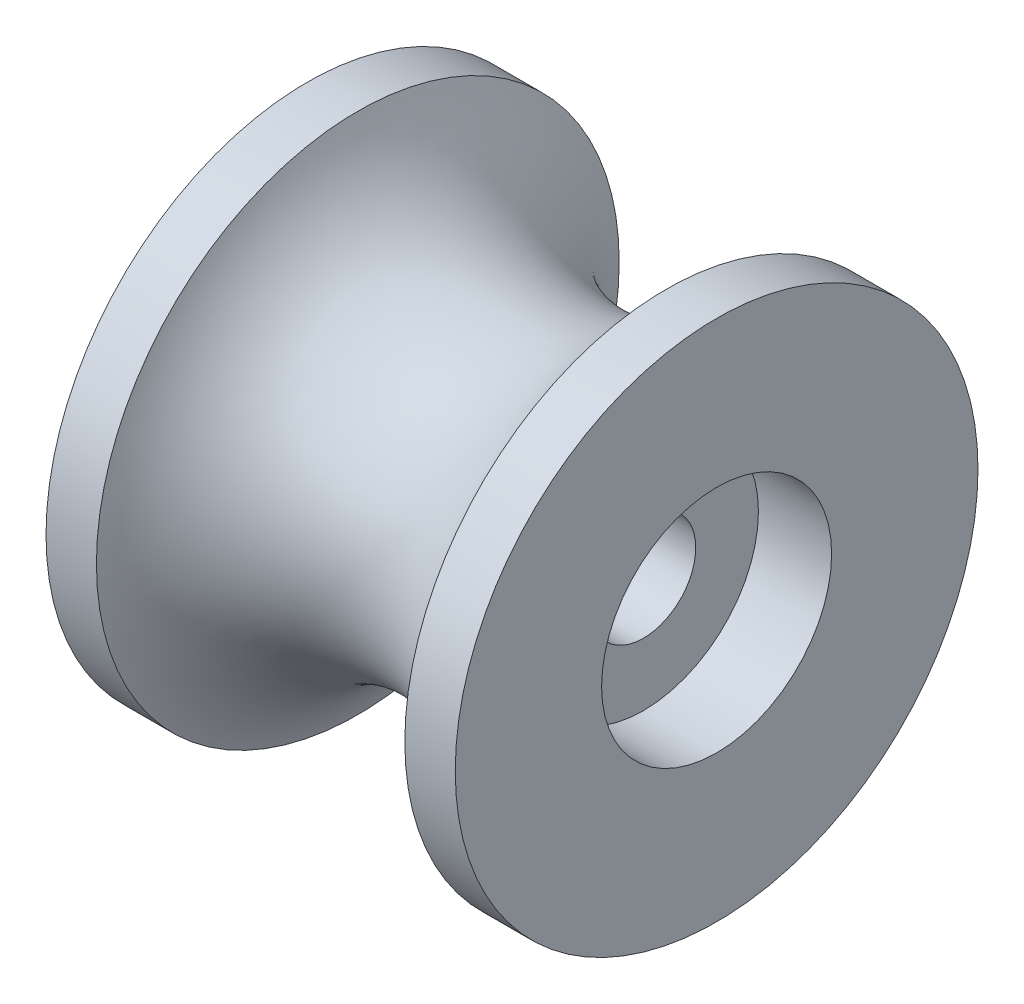
SolidWorks part; units mm, degrees
ref_plane "Front Plane" through (0, 0, 0) normal (0, 0, 1) x (1, 0, 0)
ref_plane "Top Plane" through (0, 0, 0) normal (0, 1, 0) x (1, 0, 0)
ref_plane "Right Plane" through (0, 0, 0) normal (1, 0, 0) x (0, 0, -1)
sketch "Sketch1" plane through (0, 0, 0) normal (1, 0, 0) x (0, 0, -1)
  circle A0 centre (0, 0) radius 5
  circle A1 centre (0, 0) radius 25
  dimension "D1" = 10
  dimension "D2" = 50
extrude "Boss-Extrude1" add sketch "Sketch1" along normal blind 19.57 and the other way blind 19.57
sketch "Sketch2" plane through (0, 0, 0) normal (1, 0, 0) x (0, 0, -1)
  circle A0 centre (0, 0) radius 11
  dimension "D1" = 22
extrude "Cut-Extrude1" cut sketch "Sketch2" against normal blind 7 from surface starting at face at (19.57, 0, -25)
sketch "Sketch3" plane through (0, 0, 0) normal (1, 0, 0) x (0, 0, -1)
  circle A0 centre (0, 0) radius 11
  dimension "D1" = 22
extrude "Cut-Extrude2" cut sketch "Sketch3" along normal blind 7 from surface starting at face at (-19.57, 0, -5)
sketch "Sketch4" plane through (0, 0, 0) normal (0, 0, 1) x (1, 0, 0)
  line L0 (0, 30.875) -> (0, 0) construction
  line L2 (0, 15) -> (33.0513, 15) construction
  line L3 (0, 0) -> (33.0513, 0) construction
  line L4 (33.0513, 0) -> (33.0513, 15) construction
  circle A0 centre (0, 30.875) radius 15.875
  dimension "D1" = 31.75
  dimension "D2" = 15
revolve "Cut-Revolve1" cut sketch "Sketch4" angle 360 about L3
